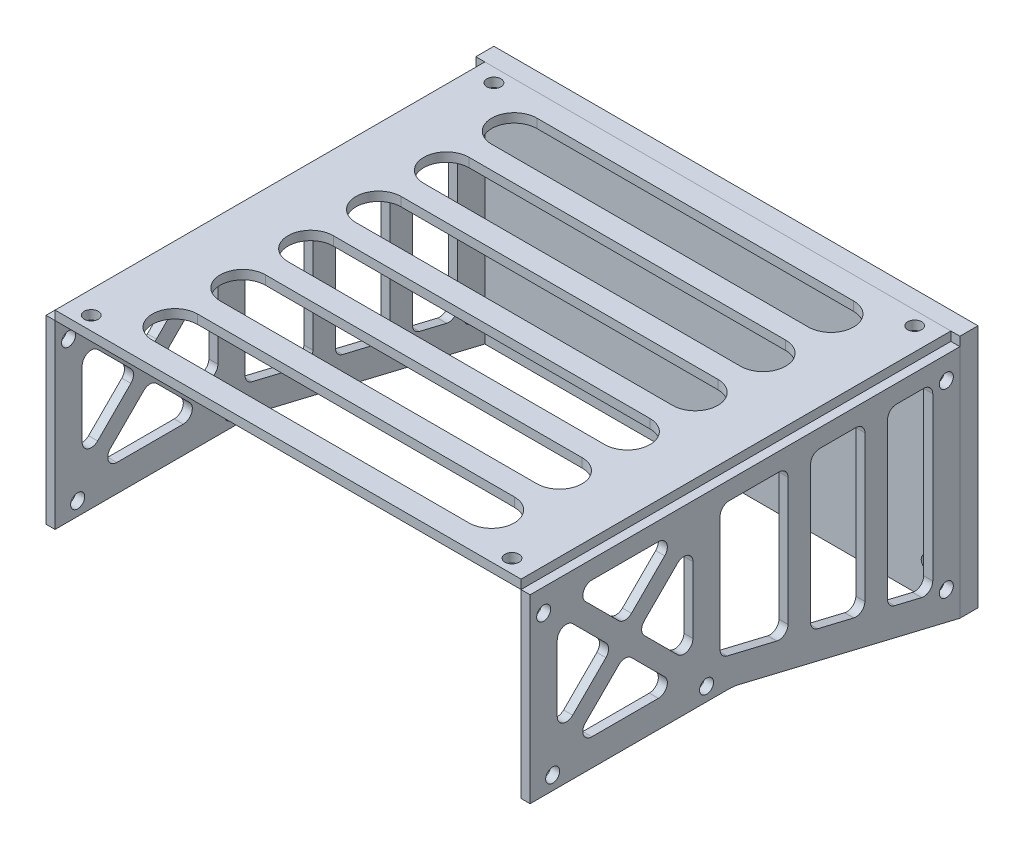
SolidWorks part; units mm, degrees
material "Thornel Mat VMA"
ref_plane "前视基准面" through (0, 0, 0) normal (0, 0, 1) x (1, 0, 0)
ref_plane "上视基准面" through (0, 0, 0) normal (0, 1, 0) x (1, 0, 0)
ref_plane "右视基准面" through (0, 0, 0) normal (1, 0, 0) x (0, 0, -1)
sketch "草图1" plane through (0, 0, 0) normal (0, 1, 0) x (1, 0, 0)
  line L0 (51.5, -44.5) -> (-51.5, -44.5) construction
  line L1 (-51.5, -47.5) -> (51.5, -47.5)
  line L2 (-51.5, -47.5) -> (-51.5, 47.5)
  line L3 (-51.5, 47.5) -> (51.5, 47.5)
  line L4 (51.5, -47.5) -> (51.5, 47.5)
  line L5 (-51.5, -47.5) -> (51.5, 47.5) construction
  line L6 (-51.5, 47.5) -> (51.5, -47.5) construction
  line L7 (0, 0) -> (0, -21.1907) construction
  line L8 (0, 0) -> (19.5366, 0) construction
  circle A0 centre (46.5, -44.5) radius 1.55
  circle A1 centre (-46.5, -44.5) radius 1.55
  circle A2 centre (-46.5, 44.5) radius 1.55
  circle A3 centre (46.5, 44.5) radius 1.55
  point P0 (0, 0)
  dimension "D4" = 3.1
  dimension "D5" = 5
  dimension "D1" = 103
  dimension "D2" = 95
  dimension "D3" = 3
extrude "凸台-拉伸1" add sketch "草图1" along normal blind 2
sketch "草图2" plane through (0, 0, 0) normal (1, 0, 0) x (0, 0, -1)
  line L0 (47.5, 2) -> (47.5, 0) construction
  line L1 (-47.5, -40) -> (-3.6832, -40)
  line L2 (-47.5, -40) -> (-47.5, 0)
  line L3 (-47.5, 0) -> (47.5, 0)
  line L4 (47.5, -40) -> (47.5, 0)
  line L5 (-47.5, -37) -> (-8.5, -37) construction
  line L6 (46.05, 2) -> (42.95, 2) construction
  line L7 (-42.95, 2) -> (-46.05, 2) construction
  line L8 (46.05, 2) -> (42.95, 2) construction
  line L9 (-42.95, 2) -> (-46.05, 2) construction
  line L10 (-44.5, 2) -> (-44.5, -5) construction
  line L11 (44.5, 2) -> (44.5, -5) construction
  line L12 (44.5, -5) -> (-44.5, -5) construction
  line L13 (47.5, -40) -> (47.5, -52)
  line L14 (47.5, -52) -> (-1.3495, -40.2761)
  line L15 (-2.5, -40) -> (47.5, -40) construction
  circle A0 centre (-8.5, -37) radius 1.55
  circle A1 centre (-42.5, -37) radius 1.55
  circle A2 centre (-44.5, -5) radius 1.55
  circle A3 centre (44.5, -5) radius 1.55
  circle A4 centre (44.5, -45) radius 1.55
  arc A5 (-1.3495, -40.2761) -> (-3.6832, -40) centre (-3.6832, -50) ccw
  dimension "D2" = 34
  dimension "D3" = 5
  dimension "D4" = 3.1
  dimension "D6" = 5
  dimension "D7" = 5
  dimension "D10" = 10
  dimension "D1" = 40
  dimension "D5" = 3
  dimension "D8" = 12
  dimension "D9" = 50
extrude "凸台-拉伸2" add sketch "草图2" against normal blind 2 from surface separate body starting at face at (-51.5, 1, 0)
extrude "凸台-拉伸3" add sketch "草图2<2>" along normal blind 2 from surface separate body starting at face at (51.5, 1, 0)
sketch "草图2<2>" plane through (0, 0, 0) normal (1, 0, 0) x (0, 0, -1) same geometry as "草图2"
sketch "草图3" plane through (0, 0, -47.5) normal (0, 0, -1) x (-1, 0, 0)
  line L0 (-51.5, 2) -> (51.5, 2) construction
  line L1 (53.5, 2) -> (-53.5, 2)
  line L2 (53.5, 2) -> (53.5, -52)
  line L3 (53.5, -52) -> (-53.5, -52)
  line L4 (-53.5, 2) -> (-53.5, -52)
  line L5 (-53.5, -52) -> (-53.5, 0) construction
  line L6 (53.5, -52) -> (53.5, 0) construction
  line L8 (-53.5, -5) -> (53.5, -5) construction
  line L9 (0, 55) -> (0, -55) construction
  line L11 (51.5, -3.45) -> (51.5, -6.55) construction
  line L13 (44.95, 0) -> (48.05, 0) construction
  line L14 (51.5, -3.45) -> (51.5, -6.55) construction
  line L15 (44.95, 0) -> (48.05, 0) construction
  line L16 (46.5, -5) -> (46.5, 0) construction
  line L17 (51.5, -43.45) -> (51.5, -46.55) construction
  line L18 (51.5, -43.45) -> (51.5, -46.55) construction
  line L19 (51.5, -45) -> (46.5, -45) construction
  circle A0 centre (46.5, -5) radius 1.55
  circle A1 centre (-46.5, -5) radius 1.55
  circle A2 centre (-46.5, -45) radius 1.55
  circle A3 centre (46.5, -45) radius 1.55
  point P27 (51.5, -5)
  dimension "D1" = 3.1
  dimension "D2" = 2
extrude "凸台-拉伸4" add sketch "草图3" along normal blind 4 separate body
sketch "草图4" plane through (0, 0, 47.5) normal (0, 0, 1) x (1, 0, 0)
  line L0 (53.5, 0) -> (53.5, -40) construction
  line L1 (-53.5, 2) -> (53.5, 2)
  line L2 (-53.5, 2) -> (-53.5, -40)
  line L3 (-53.5, -40) -> (-17.6247, -40)
  line L4 (53.5, 2) -> (53.5, -40)
  line L5 (0, 0) -> (0, -17.314) construction
  line L6 (-17.6247, -40) -> (-15.2396, -12.7385)
  line L7 (-12.251, -10) -> (12.251, -10)
  line L8 (17.6247, -40) -> (15.2396, -12.7385)
  line L9 (53.5, -40) -> (51.5, -40) construction
  line L10 (17.6247, -40) -> (53.5, -40)
  circle A0 centre (46.5, -5) radius 1.55 construction
  circle A1 centre (-46.5, -5) radius 1.55 construction
  circle A2 centre (46.5, -5) radius 1.55
  circle A3 centre (-46.5, -5) radius 1.55
  arc A4 (15.2396, -12.7385) -> (12.251, -10) centre (12.251, -13) ccw
  arc A5 (-15.2396, -12.7385) -> (-12.251, -10) centre (-12.251, -13) cw
  point P21 (0, -10)
  point P25 (15, -10)
  point P28 (-15, -10)
  dimension "D4" = 3
  dimension "D1" = 30
  dimension "D2" = 85
  dimension "D3" = 30
extrude "凸台-拉伸5" [suppressed] add sketch "草图4" along normal blind 1 separate body
sketch "草图5" plane through (0, 2, 0) normal (0, 1, 0) x (1, 0, 0)
  line L0 (35, 37.5) -> (-35, 37.5) construction
  line L1 (35, 32.5) -> (-35, 32.5)
  line L2 (35, 42.5) -> (-35, 42.5)
  line L3 (0, 0) -> (0, 103.9016) construction
  line L4 (51.5, 47.5) -> (-51.5, 47.5) construction
  line L5 (35, 27.5) -> (-35, 27.5)
  line L6 (35, 17.5) -> (-35, 17.5)
  line L7 (35, 22.5) -> (-35, 22.5) construction
  line L8 (35, 12.5) -> (-35, 12.5)
  line L9 (35, 2.5) -> (-35, 2.5)
  line L10 (35, 7.5) -> (-35, 7.5) construction
  line L11 (35, -2.5) -> (-35, -2.5)
  line L12 (35, -12.5) -> (-35, -12.5)
  line L13 (35, -7.5) -> (-35, -7.5) construction
  line L14 (35, -17.5) -> (-35, -17.5)
  line L15 (35, -27.5) -> (-35, -27.5)
  line L16 (35, -22.5) -> (-35, -22.5) construction
  line L17 (35, -32.5) -> (-35, -32.5)
  line L18 (35, -42.5) -> (-35, -42.5)
  line L19 (35, -37.5) -> (-35, -37.5) construction
  arc A0 (35, 32.5) -> (35, 42.5) centre (35, 37.5) ccw
  arc A1 (-35, 42.5) -> (-35, 32.5) centre (-35, 37.5) ccw
  arc A2 (35, 17.5) -> (35, 27.5) centre (35, 22.5) ccw
  arc A3 (-35, 27.5) -> (-35, 17.5) centre (-35, 22.5) ccw
  arc A4 (35, 2.5) -> (35, 12.5) centre (35, 7.5) ccw
  arc A5 (-35, 12.5) -> (-35, 2.5) centre (-35, 7.5) ccw
  arc A6 (35, -12.5) -> (35, -2.5) centre (35, -7.5) ccw
  arc A7 (-35, -2.5) -> (-35, -12.5) centre (-35, -7.5) ccw
  arc A8 (35, -27.5) -> (35, -17.5) centre (35, -22.5) ccw
  arc A9 (-35, -17.5) -> (-35, -27.5) centre (-35, -22.5) ccw
  arc A10 (35, -42.5) -> (35, -32.5) centre (35, -37.5) ccw
  arc A11 (-35, -32.5) -> (-35, -42.5) centre (-35, -37.5) ccw
  point P2 (0, 37.5)
  point P15 (0, 22.5)
  point P22 (0, 7.5)
  point P29 (0, -7.5)
  point P36 (0, -22.5)
  point P42 (0, -37.5)
  dimension "D2" = 5
  dimension "D1" = 70
  dimension "D3" = 5
  dimension "D5" = 15
  dimension "D4" = 6
extrude "切除-拉伸1" cut sketch "草图5" against normal through all
sketch "草图8" plane through (-53.5, 0, 0) normal (-1, 0, 0) x (0, 0, 1)
  line L0 (-47.5, -52) -> (-47.5, 0) construction
  line L1 (11.5, -4) -> (41.5, -4)
  line L2 (11.5, -4) -> (11.5, -34)
  line L3 (11.5, -34) -> (41.5, -34)
  line L4 (41.5, -4) -> (41.5, -34)
  line L5 (-41.5, -4) -> (5.5, -4)
  line L6 (-41.5, -4) -> (-41.5, -44.3896)
  line L7 (-41.5, -44.3896) -> (5.5, -33.1096)
  line L8 (5.5, -4) -> (5.5, -33.1096)
  line L9 (47.5, 0) -> (47.5, -40) construction
  line L10 (47.5, -40) -> (3.6832, -40) construction
  line L11 (-47.5, 0) -> (47.5, 0) construction
  line L12 (1.3495, -40.2761) -> (-47.5, -52) construction
  line L13 (-31.5, -4) -> (-31.5, -41.9896)
  line L14 (-26.5, -4) -> (-26.5, -40.7896)
  line L15 (-14.5, -4) -> (-14.5, -37.9096)
  line L16 (-9.5, -4) -> (-9.5, -36.7096)
  line L19 (11.5, -4) -> (41.5, -34)
  line L20 (11.5, -34) -> (41.5, -4)
  line L21 (12.9142, -35.4142) -> (42.9142, -5.4142)
  line L22 (10.0858, -32.5858) -> (40.0858, -2.5858)
  line L23 (10.0858, -5.4142) -> (40.0858, -35.4142)
  line L24 (12.9142, -2.5858) -> (42.9142, -32.5858)
  circle A0 centre (8.5, -37) radius 1.55 construction
  dimension "D1" = 6
  dimension "D2" = 6
  dimension "D3" = 6
  dimension "D4" = 3
  dimension "D5" = 4
  dimension "D6" = 6
  dimension "D7" = 6
  dimension "D8" = 5
  dimension "D9" = 5
  dimension "D10" = 12
  dimension "D11" = 10
  dimension "D14" = 2
  dimension "D15" = 2
  dimension "D16" = 2
  dimension "D17" = 2
extrude "切除-拉伸3" cut sketch "草图8" against normal through all contours L13 L5 L6 L7 | L15 L5 L14 L7 | L5 L16 L7 L8 | L23 L2 L22 | L1 L24 L22 | L21 L24 L4 | L23 L21 L3 region at (-53.5, -8.0572, 26.5) region at (-53.5, -19, 15.5572) region at (-53.5, -19, 37.4428) region at (-53.5, -29.9428, 26.5) region at (-53.5, -23.6009, -36.551) region at (-53.5, -21.6846, -20.5815) region at (-53.5, -19.4723, -2.1456)
fillet "圆角3" radius 2 24 edges at (-52.5, -31.1716, 11.5) (-52.5, -6.8284, 11.5) (-52.5, -19, 23.6716) (-52.5, -16.1716, 26.5) (-52.5, -4, 14.3284) (-52.5, -4, 38.6716) (-52.5, -31.1716, 41.5) (-52.5, -19, 29.3284) (-52.5, -6.8284, 41.5) (-52.5, -34, 14.3284) (-52.5, -21.8284, 26.5) (-52.5, -34, 38.6716) (-52.5, -44.3896, -41.5) (-52.5, -4, -31.5) (-52.5, -41.9896, -31.5) (-52.5, -40.7896, -26.5) (-52.5, -4, -26.5) (-52.5, -4, -14.5) (-52.5, -37.9096, -14.5) (-52.5, -33.1096, 5.5) (-52.5, -36.7096, -9.5) (-52.5, -4, -9.5) (-52.5, -4, 5.5) (-52.5, -4, -41.5)
fillet "圆角4" radius 2 24 edges at (52.5, -41.9896, -31.5) (52.5, -44.3896, -41.5) (52.5, -4, -31.5) (52.5, -4, 5.5) (52.5, -33.1096, 5.5) (52.5, -36.7096, -9.5) (52.5, -4, -9.5) (52.5, -4, 38.6716) (52.5, -16.1716, 26.5) (52.5, -4, 14.3284) (52.5, -34, 38.6716) (52.5, -34, 14.3284) (52.5, -21.8284, 26.5) (52.5, -6.8284, 41.5) (52.5, -31.1716, 41.5) (52.5, -19, 29.3284) (52.5, -19, 23.6716) (52.5, -31.1716, 11.5) (52.5, -6.8284, 11.5) (52.5, -37.9096, -14.5) (52.5, -40.7896, -26.5) (52.5, -4, -26.5) (52.5, -4, -14.5) (52.5, -4, -41.5)
